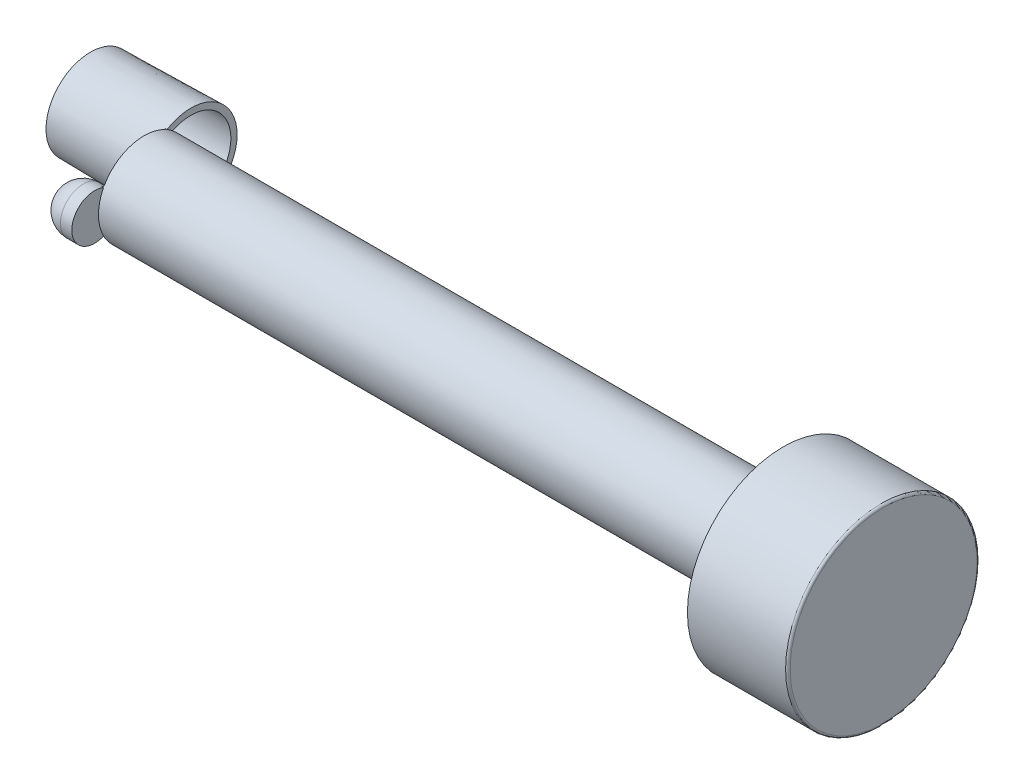
SolidWorks part; units mm, degrees
ref_plane "Front Plane" through (0, 0, 0) normal (0, 0, 1) x (1, 0, 0)
ref_plane "Top Plane" through (0, 0, 0) normal (0, 1, 0) x (1, 0, 0)
ref_plane "Right Plane" through (0, 0, 0) normal (1, 0, 0) x (0, 0, -1)
sketch "Sketch1" plane through (0, 0, 0) normal (1, 0, 0) x (0, 0, -1)
  circle A0 centre (0, 0) radius 4
  dimension "D1" = 8
extrude "Boss-Extrude1" add sketch "Sketch1" along normal blind 1
sketch "Sketch2" plane through (1, 0, 0) normal (1, 0, 0) x (0, 0, -1)
  circle A0 centre (0, 0) radius 4
  dimension "D1" = 8
extrude "Boss-Extrude2" add sketch "Sketch2" along normal blind 55
sketch "Sketch3" plane through (56, 0, 0) normal (1, 0, 0) x (0, 0, -1)
  circle A0 centre (0, 0) radius 8.39
  dimension "D1" = 16.78
extrude "Boss-Extrude3" add sketch "Sketch3" along normal blind 8.8
sketch "Sketch5" plane through (0, 0, 0) normal (-1, 0, 0) x (0, 0, 1)
  line L0 (-9.9612, 0) -> (9.2306, 0) construction
  line L1 (0, 9.1589) -> (0, -10.1785) construction
  circle A0 centre (-4.1, 0) radius 4.05
  circle A1 centre (-4.1, 0) radius 3.5
  dimension "D1" = 8.1
  dimension "D3" = 7
  dimension "D2" = 4.1
extrude "Boss-Extrude4" add sketch "Sketch5" along normal blind 8.8 draft 1
sketch "Sketch6" plane through (0, 0, 0) normal (-1, 0, 0) x (0, 0, 1)
  circle A0 centre (4.3355, 0) radius 2
  dimension "D1" = 4
extrude "Boss-Extrude5" add sketch "Sketch6" along normal blind 3
fillet "Fillet1" radius 2 1 edges at (-3, 0, 6.3355)
fillet "Fillet2" radius 0.2 1 edges at (64.8, 0, -8.39)
fillet "Fillet4" radius 0.2 2 edges at (0, 0, 2.3355) (0, 0, -0.05)
